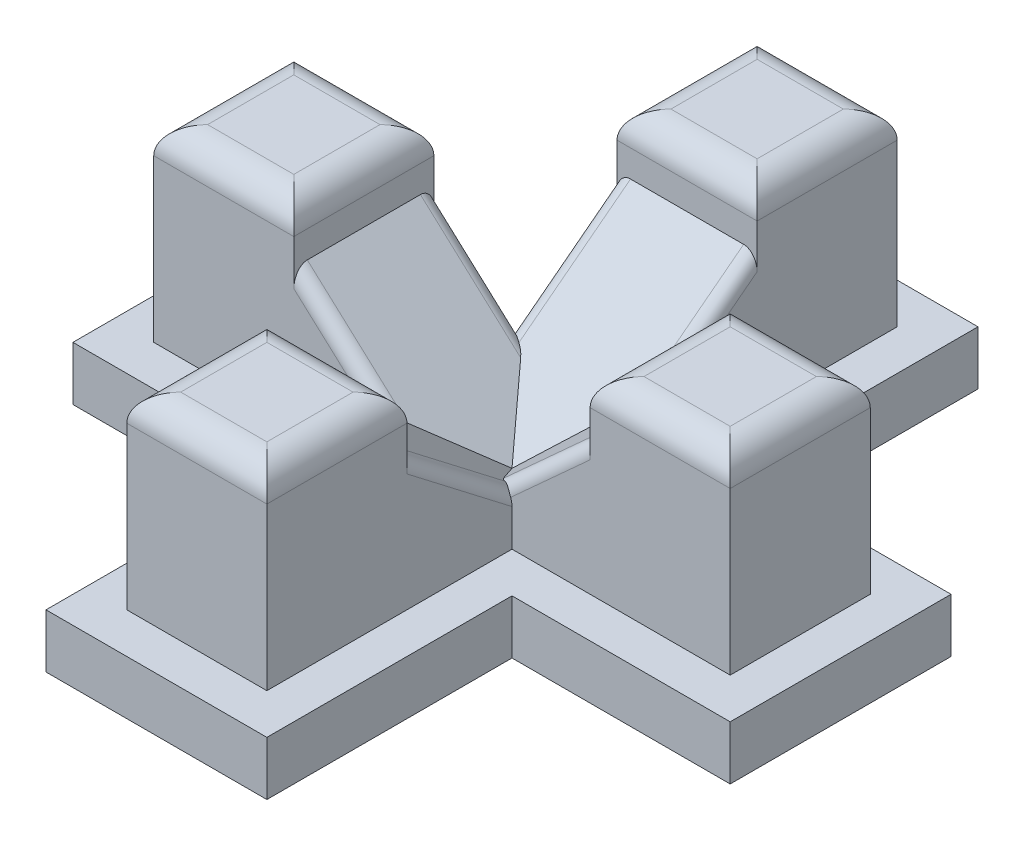
SolidWorks part; units mm, degrees
ref_plane "Front Plane" through (0, 0, 0) normal (0, 0, 1) x (1, 0, 0)
ref_plane "Top Plane" through (0, 0, 0) normal (0, 1, 0) x (1, 0, 0)
ref_plane "Right Plane" through (0, 0, 0) normal (1, 0, 0) x (0, 0, -1)
sketch "Sketch1" plane through (0, 0, 0) normal (0, 1, 0) x (1, 0, 0)
  line L0 (-4.1, 4.1) -> (-12.2, 4.1)
  line L1 (12.2, 4.1) -> (4.1, 4.1)
  line L2 (-12.2, 4.1) -> (-12.2, -4.1)
  line L3 (-12.2, -4.1) -> (-4.1, -4.1)
  line L4 (12.2, 4.1) -> (12.2, -4.1)
  line L5 (-12.2, 4.1) -> (12.2, -4.1) construction
  line L6 (-12.2, -4.1) -> (12.2, 4.1) construction
  line L7 (-4.1, 13.2) -> (4.1, 13.2)
  line L8 (-4.1, 13.2) -> (-4.1, 4.1)
  line L9 (12.2, -4.1) -> (4.1, -4.1)
  line L10 (4.1, 13.2) -> (4.1, 4.1)
  line L11 (-4.1, 13.2) -> (4.1, 4.1) construction
  line L12 (-4.1, 4.1) -> (4.1, 13.2) construction
  line L14 (-4.1, -4.1) -> (-4.1, -13.2)
  line L15 (-4.1, -13.2) -> (4.1, -13.2)
  line L16 (4.1, -4.1) -> (4.1, -13.2)
  line L17 (-4.1, -4.1) -> (4.1, -13.2) construction
  line L18 (-4.1, -13.2) -> (4.1, -4.1) construction
  line L19 (12.2, -4.1) -> (12.1894, -4.124)
  point P0 (0, 0)
  point P6 (0, 8.65)
  point P11 (0, -8.65)
  dimension "D1" = 24.4
  dimension "D2" = 8.2
  dimension "D3" = 8.2
  dimension "D4" = 0
  dimension "D5" = 8.1
  dimension "D6" = 9.1
  dimension "D7" = 9.1
  dimension "D8" = 8.2
  dimension "D9" = 8.1
  dimension "D10" = 0
extrude "Boss-Extrude1" add sketch "Sketch1" along normal blind 2 contours L16 L9 L4 L1 L10 L7 L8 L0 L2 L3 L14 L15 region at (0, 0, 0)
sketch "Sketch4" plane through (0, 2, 0) normal (0, 1, 0) x (1, 0, 0)
  line L0 (12.2, 4.1) -> (12.2, -4.1) construction
  line L1 (10.7, -2.6) -> (5.5, -2.6)
  line L2 (10.7, -2.6) -> (10.7, 2.6)
  line L3 (10.7, 2.6) -> (5.5, 2.6)
  line L4 (5.5, -2.6) -> (5.5, 2.6)
  line L5 (10.7, -2.6) -> (5.5, 2.6) construction
  line L6 (10.7, 2.6) -> (5.5, -2.6) construction
  line L7 (2.6, -11.7) -> (-2.6, -11.7)
  line L8 (2.6, -11.7) -> (2.6, -6.5)
  line L9 (2.6, -6.5) -> (-2.6, -6.5)
  line L10 (-2.6, -11.7) -> (-2.6, -6.5)
  line L11 (2.6, -11.7) -> (-2.6, -6.5) construction
  line L12 (2.6, -6.5) -> (-2.6, -11.7) construction
  line L13 (2.6, 6.5) -> (-2.6, 6.5)
  line L14 (2.6, 6.5) -> (2.6, 11.7)
  line L15 (2.6, 11.7) -> (-2.6, 11.7)
  line L16 (-2.6, 6.5) -> (-2.6, 11.7)
  line L17 (2.6, 6.5) -> (-2.6, 11.7) construction
  line L18 (2.6, 11.7) -> (-2.6, 6.5) construction
  line L19 (-5.5, -2.6) -> (-10.7, -2.6)
  line L20 (-5.5, -2.6) -> (-5.5, 2.6)
  line L21 (-5.5, 2.6) -> (-10.7, 2.6)
  line L22 (-10.7, -2.6) -> (-10.7, 2.6)
  line L23 (-5.5, -2.6) -> (-10.7, 2.6) construction
  line L24 (-5.5, 2.6) -> (-10.7, -2.6) construction
  line L25 (12.2, 4.1) -> (4.1, 4.1) construction
  line L26 (4.1, 13.2) -> (4.1, 4.1) construction
  line L27 (-4.1, 13.2) -> (4.1, 13.2) construction
  line L28 (-4.1, 4.1) -> (-12.2, 4.1) construction
  line L31 (-12.2, 4.1) -> (-12.2, -4.1) construction
  line L32 (4.1, -4.1) -> (4.1, -13.2) construction
  line L33 (-4.1, -13.2) -> (4.1, -13.2) construction
  point P0 (8.1, 0)
  point P5 (0, -9.1)
  point P10 (0, 9.1)
  point P15 (-8.1, 0)
  dimension "D1" = 5.2
  dimension "D2" = 5.2
  dimension "D3" = 1.5
  dimension "D4" = 1.5
  dimension "D5" = 5.2
  dimension "D6" = 5.2
  dimension "D7" = 5.2
  dimension "D8" = 5.2
  dimension "D9" = 5.2
  dimension "D10" = 5.2
  dimension "D11" = 1.5
  dimension "D12" = 1.5
  dimension "D13" = 1.5
  dimension "D14" = 1.5
  dimension "D15" = 1.5
  dimension "D16" = 1.5
extrude "Boss-Extrude3" add sketch "Sketch4" along normal blind 7
fillet "Fillet6" radius 1 16 edges at (-2.6, 9, -9.1) (0, 9, -11.7) (2.6, 9, -9.1) (0, 9, -6.5) (-5.5, 9, 0) (-8.1, 9, 2.6) (-10.7, 9, 0) (-8.1, 9, -2.6) (-2.6, 9, 9.1) (0, 9, 6.5) (2.6, 9, 9.1) (0, 9, 11.7) (8.1, 9, 2.6) (5.5, 9, 0) (10.7, 9, 0) (8.1, 9, -2.6)
sketch "Sketch5" plane through (0, 0, -2.6) normal (0, 0, -1) x (-1, 0, 0)
  line L0 (-5.5, 2) -> (-5.5, 6.9979)
  line L1 (-5.5, 8) -> (-5.5, 2) construction
  line L2 (-5.5, 2) -> (0, 2)
  line L3 (0, 2) -> (-5.5, 6.9979)
extrude "Boss-Extrude4" add sketch "Sketch5" against normal blind 5.2
sketch "Sketch6" plane through (2.6, 0, 0) normal (1, 0, 0) x (0, 0, -1)
  line L0 (6.5, 2) -> (6.5, 7)
  line L1 (6.5, 8) -> (6.5, 2) construction
  line L2 (6.5, 2) -> (0, 2)
  line L3 (0, 2) -> (6.5, 7)
  dimension "D1" = 5
extrude "Boss-Extrude5" add sketch "Sketch6" against normal blind 5.2
sketch "Sketch7" plane through (0, 0, -2.6) normal (0, 0, -1) x (-1, 0, 0)
  line L0 (5.5, 2) -> (5.5, 7)
  line L1 (5.5, 8) -> (5.5, 2) construction
  line L2 (5.5, 2) -> (0, 2)
  line L3 (0, 2) -> (5.5, 7)
  dimension "D1" = 5
extrude "Boss-Extrude6" add sketch "Sketch7" against normal blind 5.2
sketch "Sketch8" plane through (-2.6, 0, 0) normal (-1, 0, 0) x (0, 0, 1)
  line L0 (6.5, 2) -> (6.5, 7)
  line L1 (6.5, 8) -> (6.5, 2) construction
  line L2 (6.5, 2) -> (0, 2)
  line L3 (0, 2) -> (6.5, 7)
  dimension "D1" = 5
extrude "Boss-Extrude7" add sketch "Sketch8" against normal blind 5.2
fillet "Fillet7" radius 0.5 8 edges at (2.6, 5.5, -4.55) (3.8505, 5.499, -2.6) (-2.6, 5.5, -4.55) (-3.85, 5.5, -2.6) (-3.85, 5.5, 2.6) (-2.6, 5.5, 4.55) (2.6, 5.5, 4.55) (3.8505, 5.499, 2.6)
